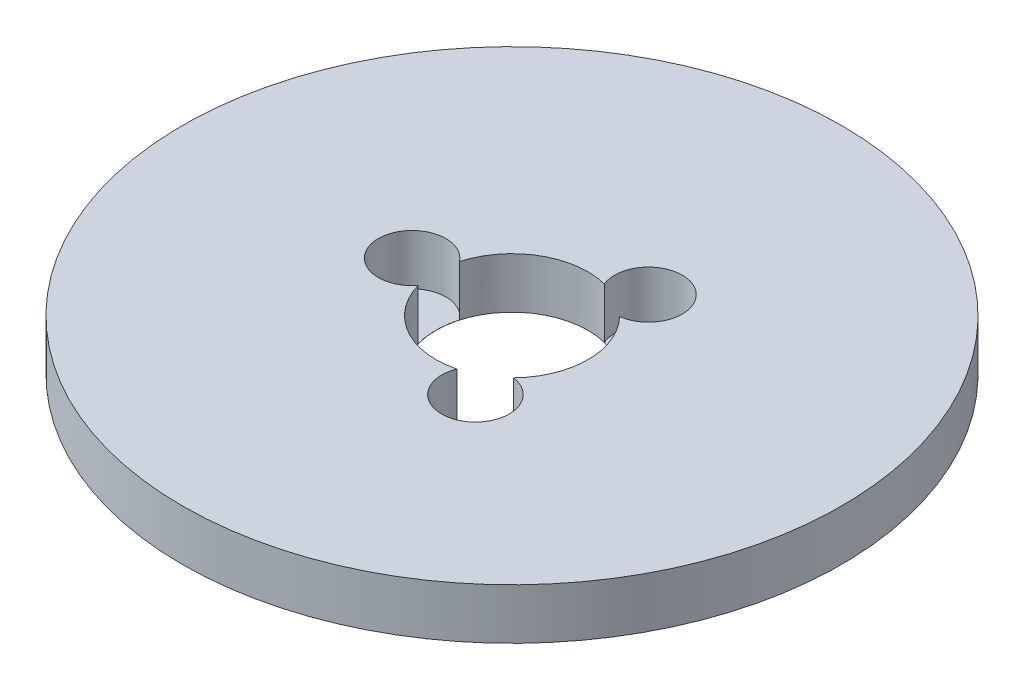
SolidWorks part; units mm, degrees
ref_plane "Front Plane" through (0, 0, 0) normal (0, 0, 1) x (1, 0, 0)
ref_plane "Top Plane" through (0, 0, 0) normal (0, 1, 0) x (1, 0, 0)
ref_plane "Right Plane" through (0, 0, 0) normal (1, 0, 0) x (0, 0, -1)
sketch "Sketch1" plane through (0, 0, 0) normal (0, 1, 0) x (1, 0, 0)
  circle A0 centre (0, 0) radius 97.5
  dimension "FLANGE_OD" = 195
extrude "Boss-Extrude1" add sketch "Sketch1" along normal blind 15
sketch "Sketch2" plane through (0, 0, 0) normal (0, 1, 0) x (1, 0, 0)
  circle A0 centre (0, 0) radius 22.5
  dimension "BORE_D" = 45
extrude "Cut-Extrude1" cut sketch "Sketch2" along normal through all
sketch "Sketch3" plane through (0, 15, 0) normal (0, 1, 0) x (1, 0, 0)
  circle A0 centre (0, 0) radius 29.5561 construction
  circle A1 centre (-29.5561, 0) radius 10
  dimension "BOLT_D" = 20
  dimension "BOLT_PCD" = 59.1122
extrude "Cut-Extrude2" cut sketch "Sketch3" against normal blind 14.9605
pattern_circular "CirPattern1" count 3 over 360 about axis through (0, 0, 0) along (0, 1, 0) of "Cut-Extrude2"
